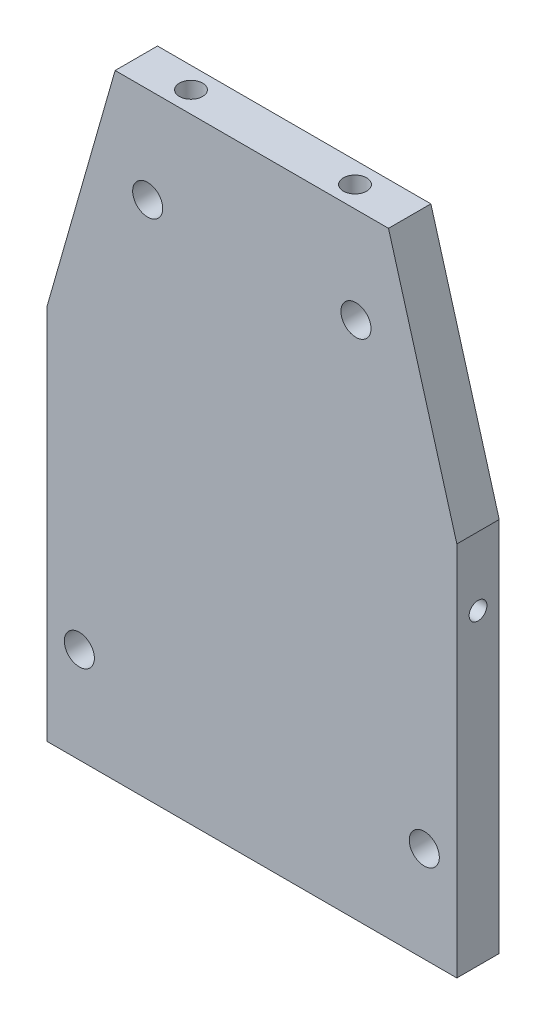
SolidWorks part; units mm, degrees
material "6061 Alloy"
ref_plane "Front Plane" through (0, 0, 0) normal (0, 0, 1) x (1, 0, 0)
ref_plane "Top Plane" through (0, 0, 0) normal (0, 1, 0) x (1, 0, 0)
ref_plane "Right Plane" through (0, 0, 0) normal (1, 0, 0) x (0, 0, -1)
sketch "Sketch1" plane through (0, 0, 0) normal (0, 0, 1) x (1, 0, 0)
  line L0 (-20, 45) -> (20, 45)
  line L5 (-30, -45) -> (30, -45)
  line L6 (0, 45) -> (0, -45) construction
  line L7 (-20, 45) -> (-30, 10)
  line L8 (-30, 10) -> (-30, -45)
  line L9 (30, 10) -> (30, -45)
  line L10 (20, 45) -> (30, 10)
  dimension "D1" = 90
  dimension "D2" = 60
  dimension "D3" = 40
  dimension "D4" = 55
extrude "1/4" add sketch "Sketch1" along normal mid plane 6.2
sketch "Sketch4" plane through (0, 45, 0) normal (0, 1, 0) x (1, 0, 0)
  line L0 (0, -3.1) -> (0, 3.1) construction
  line L1 (0, 0) -> (-12, 0) construction
  line L2 (20, -3.1) -> (-20, -3.1) construction
  line L3 (20, 3.1) -> (-20, 3.1) construction
  circle A0 centre (-12, 0) radius 1.7
  circle A1 centre (12, 0) radius 1.7
  dimension "D2" = 3.4
  dimension "D1" = 12
extrude "M4_DRILL" cut sketch "Sketch4" against normal blind 8
sketch "Sketch5" plane through (0, -45, 0) normal (0, -1, 0) x (-1, 0, 0)
  line L0 (0, -3.1) -> (0, 3.1) construction
  line L2 (0, 0) -> (-20, 0) construction
  line L3 (30, -3.1) -> (-30, -3.1) construction
  line L4 (30, 3.1) -> (-30, 3.1) construction
  circle A0 centre (-20, 0) radius 1.7
  circle A1 centre (20, 0) radius 1.7
  circle A2 centre (0, 0) radius 1.7
  dimension "D1" = 3.4
  dimension "D2" = 20
extrude "M4_DRILL2" cut sketch "Sketch5" against normal blind 8
sketch "Sketch6" plane through (0, 0, 3.1) normal (0, 0, 1) x (1, 0, 0)
  line L0 (-30, -45) -> (30, -45) construction
  line L1 (-30, 10) -> (-30, -45) construction
  line L2 (0, 0) -> (0, -17.9243) construction
  line L3 (20, 45) -> (-20, 45) construction
  circle A0 centre (-25.2375, -31) radius 2.2
  circle A1 centre (25.2375, -31) radius 2.2
  circle A2 centre (-15.2375, 31) radius 2.2
  circle A3 centre (15.2375, 31) radius 2.2
  dimension "D1" = 4.4
  dimension "D6" = 4.4
  dimension "D2" = 14
  dimension "D3" = 4.7625
  dimension "D4" = 14
  dimension "D5" = 4.7625
extrude "M4_through" cut sketch "Sketch6" against normal up to surface (6.2 mm away) up to face at (0, 3.3333, -3.1)
sketch "Sketch7" plane through (-30, 0, 0) normal (-1, 0, 0) x (0, 0, 1)
  circle A0 centre (0, 0) radius 1.3
  dimension "D1" = 2.6
extrude "M3_Drill" cut sketch "Sketch7" against normal blind 10
mirror "Mirror1" about plane through (0, 0, 0) normal (1, 0, 0) of "M3_Drill"
